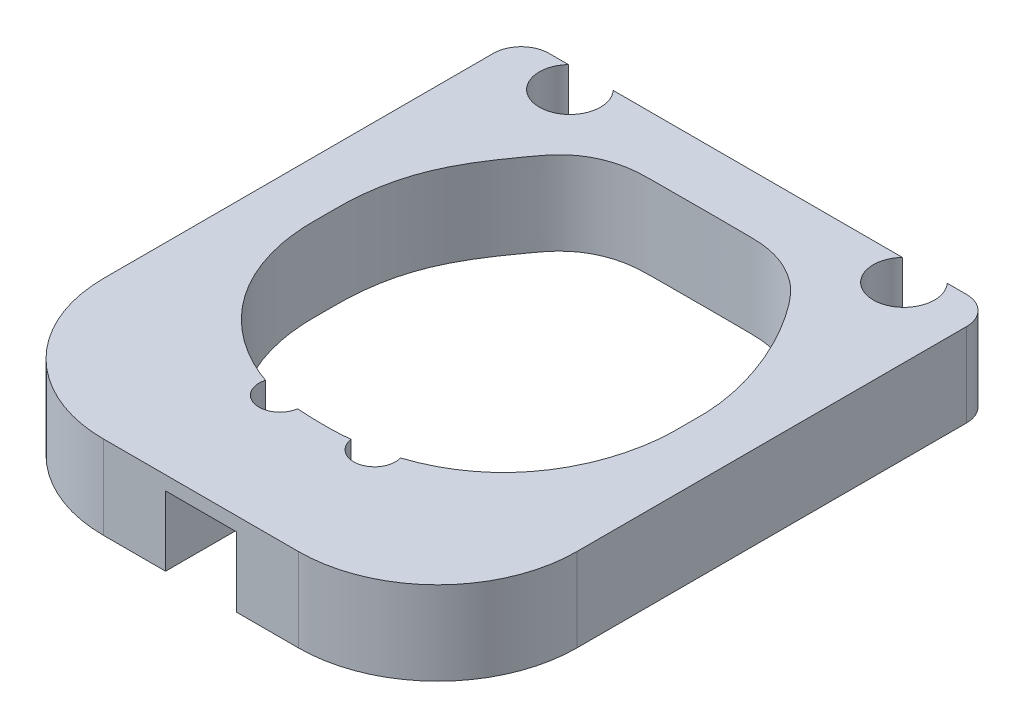
SolidWorks part; units mm, degrees
ref_plane "Plan de face" through (0, 0, 0) normal (0, 0, 1) x (1, 0, 0)
ref_plane "Plan de dessus" through (0, 0, 0) normal (0, 1, 0) x (1, 0, 0)
ref_plane "Plan de droite" through (0, 0, 0) normal (1, 0, 0) x (0, 0, -1)
ref_plane "Plan1" through (0, 0, 0) normal (0, 1, 0) x (1, 0, 0)
sketch "Esquisse1" plane through (0, 0, 0) normal (0, 1, 0) x (1, 0, 0)
  line L1 (-7.5, 9) -> (7.5, 9)
  line L2 (-8.5, 8) -> (-8.5, -6)
  line L3 (-3.5, -11) -> (3.5, -11)
  line L4 (8.5, 8) -> (8.5, -6)
  arc A0 (-3.5, -11) -> (-8.5, -6) centre (-3.5, -6) cw
  arc A1 (8.5, -6) -> (3.5, -11) centre (3.5, -6) cw
  arc A2 (-7.5, 9) -> (-8.5, 8) centre (-7.5, 8) ccw
  arc A3 (7.5, 9) -> (8.5, 8) centre (7.5, 8) cw
  spline S0 degree 3 poles (-6.4938, -0.2013) (-6.572, 2.567) (-5.6328, 4.1026) (-3.9037, 6.4469) (-2.7582, 6.8993) (-0.8788, 6.9122) (1.1301, 6.9137) (2.7624, 6.8946) (3.9133, 6.3937) (5.6838, 4.1829) (6.5548, 1.8243) (6.4943, -0.0064) (6.5124, -0.675) (6.2456, -3.4367) (4.3253, -6.1825) (0.5423, -6.62) (-0.4249, -6.6075) (-3.0912, -6.4783) (-6.1228, -4.404) (-6.517, -0.7729) (-6.4938, -0.2013) (-6.572, 2.567) (-5.6328, 4.1026) knots -0.028087 -0.008777 -0.000975 0 0.112372 0.130276 0.173621 0.187169 0.252205 0.26694 0.319781 0.34342 0.479691 0.498677 0.514296 0.542967 0.756721 0.785787 0.80456 0.825241 0.971913 0.991223 0.999025 1 1.112372 1.130276 1.173621 only from (-6.5, 0.0214) to (-6.5, 0.0214)
  point P0 (-4.3092, 5.8708)
  point P1 (-2.0473, 6.9)
  point P3 (2.0473, 6.9)
  point P5 (4.3092, 5.8708)
  point P9 (6.5, 0.0214)
  point P10 (8.5, -11)
  point P11 (6.5, -0.6)
  point P13 (0.5, -6.6)
  point P15 (-0.5, -6.6)
  point P17 (-8.5, 9)
  point P19 (-6.5, -0.6)
  point P21 (-6.5, 0.0214)
  point P24 (8.5, 9)
  dimension "D5" = 5
  dimension "D6" = 5
  dimension "D7" = 1
  dimension "D8" = 1
  dimension "D1" = 20
  dimension "D2" = 17
  dimension "D3" = 8.5
  dimension "D4" = 11
extrude "Boss.-Extru.1" add sketch "Esquisse1" along normal blind 3
sketch "Esquisse3" plane through (0, 3, 0) normal (0, 1, 0) x (1, 0, 0)
  line L0 (0, 0) -> (0, -3.4245) construction
  circle A0 centre (-1.7, -6.4677) radius 0.75
  circle A2 centre (1.7, -6.4677) radius 0.75
  spline S1 degree 3 poles (-5.6328, 4.1026) (-6.572, 2.567) (-6.4938, -0.2013) (-6.517, -0.7729) (-6.1228, -4.404) (-3.0912, -6.4783) (-0.4249, -6.6075) (0.5423, -6.62) (4.3253, -6.1825) (6.2456, -3.4367) (6.5124, -0.675) (6.4943, -0.0064) (6.5548, 1.8243) (5.6838, 4.1829) (3.9133, 6.3937) (2.7624, 6.8946) (1.1301, 6.9137) (-0.8788, 6.9122) (-2.7582, 6.8993) (-3.9037, 6.4469) (-5.6328, 4.1026) (-6.572, 2.567) (-6.4938, -0.2013) knots -0.173621 -0.130276 -0.112372 0 0.000975 0.008777 0.028087 0.174759 0.19544 0.214213 0.243279 0.457033 0.485704 0.501323 0.520309 0.65658 0.680219 0.73306 0.747795 0.812831 0.826379 0.869724 0.887628 1 1.000975 1.008777 1.028087 only from (-6.5, 0.0214) to (-6.5, 0.0214) construction
  dimension "D2" = 1.5
  dimension "D1" = 1.7
extrude "Enlèv. mat.-Extru.1" cut sketch "Esquisse3" against normal blind 3
sketch "Esquisse4" plane through (0, 0, 0) normal (0, -1, 0) x (1, 0, 0)
  line L5 (-3.5, 11) -> (3.5, 11) construction
  line L6 (-1.275, 11) -> (1.275, 11)
  line L7 (1.275, 11) -> (1.275, 8.5)
  line L8 (1.275, 8.5) -> (-1.275, 8.5)
  line L9 (-1.275, 8.5) -> (-1.275, 11)
  line L10 (-6, -8.25) -> (6, -8.25) construction
  line L11 (0, 11) -> (0, -8.25) construction
  line L12 (7.5, -9) -> (-7.5, -9) construction
  circle A0 centre (-6, -8.25) radius 1.1
  circle A1 centre (6, -8.25) radius 1.1
  point P0 (0, 11)
  point P14 (0, 0)
  line M10 (-7.5, -9) -> (7.5, -9)
  dimension "D3" = 12
  dimension "D4" = 2.2
  dimension "D1" = 2.55
  dimension "D2" = 2.5
  dimension "D5" = 0.75
extrude "Enlèv. mat.-Extru.2" cut sketch "Esquisse4" against normal blind 2.5 contours L9 L6 L7 L8
extrude "Enlèv. mat.-Extru.3" cut sketch "Esquisse4<3>" against normal up to next contours A0 M10 | A1 M10 region at (-6, 0, -8.1482) region at (6, 0, -8.1482)
sketch "Esquisse4<3>" plane through (0, 0, 0) normal (0, -1, 0) x (1, 0, 0) same geometry as "Esquisse4"
equation "\"D3@Esquisse1\"=\"D2@Esquisse1\"/2"
